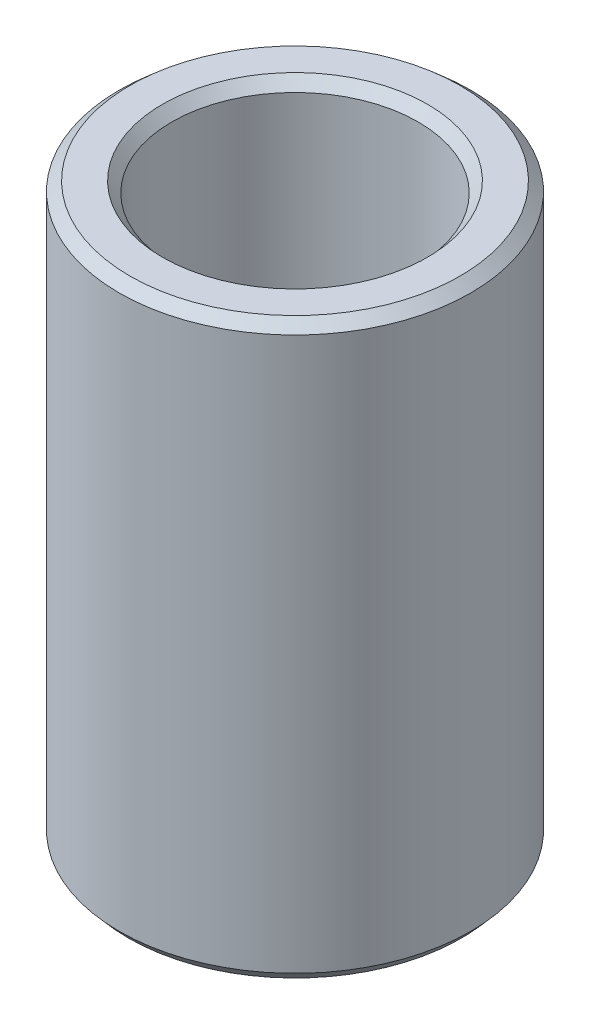
SolidWorks part; units mm, degrees
ref_plane "Front Plane" through (0, 0, 0) normal (0, 0, 1) x (1, 0, 0)
ref_plane "Top Plane" through (0, 0, 0) normal (0, 1, 0) x (1, 0, 0)
ref_plane "Right Plane" through (0, 0, 0) normal (1, 0, 0) x (0, 0, -1)
sketch "Sketch1" plane through (0, 0, 0) normal (0, 1, 0) x (1, 0, 0)
  circle A0 centre (0, 0) radius 42.5
  dimension "SLEEVE_OD" = 85
extrude "Boss-Extrude1" add sketch "Sketch1" along normal blind 138.5221
sketch "Sketch2" plane through (0, 0, 0) normal (0, 1, 0) x (1, 0, 0)
  circle A0 centre (0, 0) radius 29.7974
  dimension "BORE_D" = 59.5947
extrude "Cut-Extrude1" cut sketch "Sketch2" along normal through all
chamfer "Chamfer1" distance 2.2595 angle 48.73 4 edges at (0, 138.5221, 29.7974) (0, 0, 29.7974) (0, 0, 42.5) (0, 138.5221, 42.5) first distance on face at (0, 138.5221, 29.7974) first distance on face at (0, 0, 29.7974) first distance on face at (0, 138.5221, 42.5)
